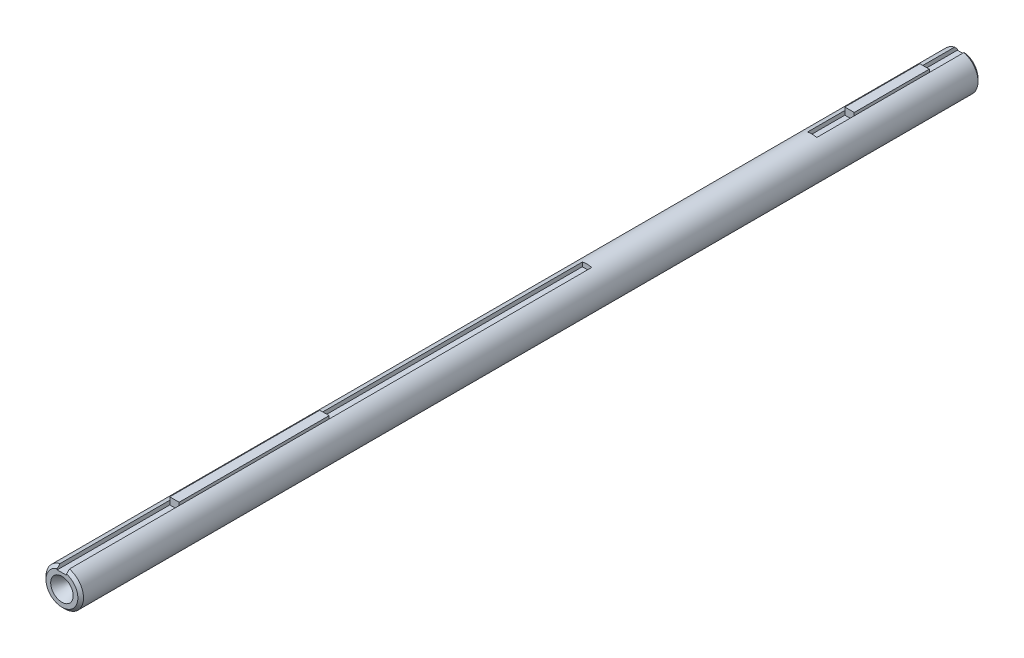
SolidWorks part; units mm, degrees
ref_plane "Front" through (0, 0, 0) normal (0, 0, 1) x (1, 0, 0)
ref_plane "Top" through (0, 0, 0) normal (0, 1, 0) x (1, 0, 0)
ref_plane "Right" through (0, 0, 0) normal (1, 0, 0) x (0, 0, -1)
sketch "Sketch1" plane through (0, 0, 0) normal (0, 0, 1) x (1, 0, 0)
  circle A0 centre (0, 0) radius 12.7
  dimension "dia" = 25.4
extrude "Extrude1" add sketch "Sketch1" along normal mid plane 609.6
sketch "Sketch2" plane through (0, 0, 0) normal (1, 0, 0) x (0, 0, -1)
  point P0 (-304.8, 12.7)
  point P1 (304.8, 12.7)
  point P2 (304.8, -12.7)
chamfer "Chamfer1" distance 1.905 angle 45 2 edges at (12.7, 0, -304.8) (12.7, 0, 304.8)
sketch "Sketch3" plane through (0, 0, 0) normal (0, 0, 1) x (1, 0, 0)
  line L1 (-3.175, 12.7) -> (3.175, 12.7)
  line L2 (-3.175, 12.7) -> (-3.175, 9.525)
  line L3 (-3.175, 9.525) -> (3.175, 9.525)
  line L4 (3.175, 12.7) -> (3.175, 9.525)
  dimension "key wd" = 6.35
  dimension "key dp" = 3.175
extrude "Extrude2" cut sketch "Sketch3" against normal through all and the other way through all
extrude "Extrude3" add sketch "Sketch1<2>" along normal offset from surface 355.6 and the other way offset from surface 101.6 from offset 101.6 up to face at (0, 4.6431, 304.8) other way up to face at (0, 4.6431, -304.8) offset against normal yes
sketch "Sketch1<2>" plane through (0, 0, 0) normal (0, 0, 1) x (1, 0, 0) same geometry as "Sketch1"
ref_plane "Plane1" through (0, 0, 228.6) normal (0, 0, 1) x (1, 0, 0)
ref_plane "Plane2" through (0, 0, -254) normal (0, 0, -1) x (-1, 0, 0)
sketch "Sketch5" plane through (0, 0, 228.6) normal (0, 0, 1) x (1, 0, 0)
  line L1 (3.175, 12.7) -> (3.175, 9.525) construction
  line L2 (-3.175, 9.525) -> (3.175, 9.525) construction
  line L3 (-3.175, 12.7) -> (-3.175, 9.525) construction
  line L4 (-3.175, 14.2875) -> (3.175, 14.2875)
  line L5 (3.175, 14.2875) -> (3.175, 9.525)
  line L6 (-3.175, 9.525) -> (3.175, 9.525)
  line L7 (-3.175, 14.2875) -> (-3.175, 9.525)
  dimension "D1" = 4.7625
extrude "Extrude4" add sketch "Sketch5" against normal blind 101.6 separate body
sketch "Sketch6" plane through (0, 0, -254) normal (0, 0, -1) x (-1, 0, 0)
  line L4 (3.175, 14.2875) -> (-3.175, 14.2875)
  line L5 (-3.175, 14.2875) -> (-3.175, 9.525)
  line L6 (-3.175, 9.525) -> (3.175, 9.525)
  line L7 (3.175, 9.525) -> (3.175, 14.2875)
  line L8 (3.175, 14.2875) -> (-3.175, 14.2875)
  line L9 (-3.175, 14.2875) -> (-3.175, 9.525)
  line L10 (-3.175, 9.525) -> (3.175, 9.525)
  line L11 (3.175, 9.525) -> (3.175, 14.2875)
  dimension "D1" = 0
extrude "Extrude5" add sketch "Sketch6" along normal mid plane 50.8 separate body
sketch "Sketch7" plane through (0, 0, 304.8) normal (0, 0, 1) x (1, 0, 0)
  circle A0 centre (0, 0) radius 3.175
  dimension "D1" = 6.35
sketch "Sketch8" plane through (0, 0, 0) normal (1, 0, 0) x (0, 0, -1)
  line L0 (304.8, -0.2387) -> (-304.8, -0.2387) construction
  line L1 (304.8, -10.795) -> (304.8, 10.3175) construction
  line L2 (-304.8, 10.3175) -> (-304.8, -10.795) construction
  line L3 (-304.8, -0.2387) -> (-288.8789, -0.2387)
  line L5 (-288.8789, -0.2387) -> (-290.751, 2.9363)
  line L6 (-290.751, 2.9363) -> (-297.101, 2.9363)
  line L7 (-297.101, 2.9363) -> (-304.8, 7.3813)
  line L8 (-304.8, 7.3813) -> (-309.9849, 7.3813)
  line L9 (-309.9849, 7.3813) -> (-309.9849, -0.2387)
  line L10 (-309.9849, -0.2387) -> (-304.8, -0.2387)
  dimension "D1" = 3.175
  dimension "D2" = 60
  dimension "D3" = 7.62
  dimension "D4" = 6.35
revolve "Cut-Revolve1" cut sketch "Sketch8" angle 360 about L0
mirror "Mirror1" about plane through (0, 0, 0) normal (0, 0, 1) of "Cut-Revolve1"
equation "\"D1@Chamfer1\" = \"dia@Sketch1\" * .075"
equation "\"D1@Sketch5\" = \"key dp@Sketch3\" * 1.5"
